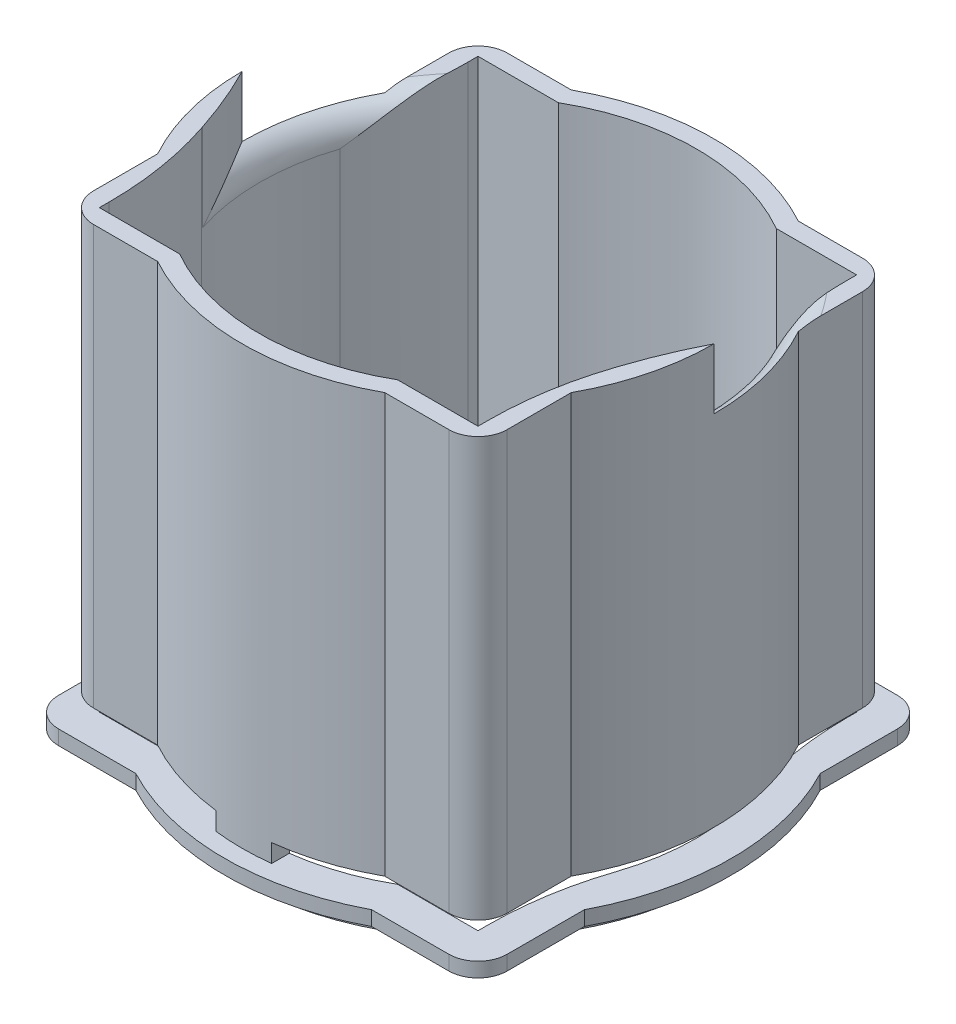
SolidWorks part; units mm, degrees
ref_plane "Front Plane" through (0, 0, 0) normal (0, 0, 1) x (1, 0, 0)
ref_plane "Top Plane" through (0, 0, 0) normal (0, 1, 0) x (1, 0, 0)
ref_plane "Right Plane" through (0, 0, 0) normal (1, 0, 0) x (0, 0, -1)
sketch "Sketch1" plane through (0, 0, 0) normal (0, 1, 0) x (1, 0, 0)
  line L0 (23.7595, 41.275) -> (41.275, 41.275)
  line L1 (-41.275, -41.275) -> (-23.7595, -41.275)
  line L2 (-41.275, -41.275) -> (-41.275, -23.7595)
  line L3 (-41.275, 41.275) -> (-23.7595, 41.275)
  line L4 (41.275, -41.275) -> (41.275, -23.7595)
  line L5 (-41.275, -41.275) -> (41.275, 41.275) construction
  line L6 (-41.275, 41.275) -> (41.275, -41.275) construction
  line L7 (41.275, 23.7595) -> (41.275, 41.275)
  line L8 (-41.275, 23.7595) -> (-41.275, 41.275)
  line L9 (23.7595, -41.275) -> (41.275, -41.275)
  line L10 (24.7569, 45.085) -> (45.085, 45.085)
  line L11 (45.085, 24.7569) -> (45.085, 45.085)
  line L12 (45.085, -45.085) -> (45.085, -24.7569)
  line L13 (24.7569, -45.085) -> (45.085, -45.085)
  line L14 (-45.085, -45.085) -> (-24.7569, -45.085)
  line L15 (-45.085, -45.085) -> (-45.085, -24.7569)
  line L16 (-45.085, 24.7569) -> (-45.085, 45.085)
  line L17 (-45.085, 45.085) -> (-24.7569, 45.085)
  arc A1 (-41.275, 23.7595) -> (-41.275, -23.7595) centre (0, 0) ccw
  arc A2 (23.7595, 41.275) -> (-23.7595, 41.275) centre (0, 0) ccw
  arc A3 (-23.7595, -41.275) -> (23.7595, -41.275) centre (0, 0) ccw
  arc A4 (41.275, -23.7595) -> (41.275, 23.7595) centre (0, 0) ccw
  arc A5 (45.085, -24.7569) -> (45.085, 24.7569) centre (0, 0) ccw
  arc A6 (-24.7569, -45.085) -> (24.7569, -45.085) centre (0, 0) ccw
  arc A7 (-45.085, 24.7569) -> (-45.085, -24.7569) centre (0, 0) ccw
  arc A8 (24.7569, 45.085) -> (-24.7569, 45.085) centre (0, 0) ccw
  point P0 (0, 0)
  dimension "D1" = 82.55
  dimension "D2" = 82.55
  dimension "D3" = 95.25
  dimension "D4" = 3.81
extrude "Boss-Extrude1" add sketch "Sketch1" along normal blind 101.6
sketch "Sketch6" plane through (0, 0, 0) normal (0, 0, 1) x (1, 0, 0)
  line L1 (-56.642, 10.287) -> (-6.096, 10.287)
  line L2 (-56.642, 10.287) -> (-56.642, 6.35)
  line L3 (-56.642, 6.35) -> (-6.096, 6.35)
  line L5 (-45.085, 0) -> (-24.7569, 0) construction
  line L8 (-6.096, 10.287) -> (-6.096, 6.35)
  line L9 (0, 0) -> (0, 21.9448) construction
  line L10 (6.096, 10.287) -> (6.096, 6.35)
  line L11 (56.642, 6.35) -> (6.096, 6.35)
  line L12 (56.642, 10.287) -> (6.096, 10.287)
  line L13 (56.642, 10.287) -> (56.642, 6.35)
  dimension "D3" = 3.937
  dimension "D1" = 6.096
  dimension "D4" = 6.35
extrude "Cut-Extrude4" cut sketch "Sketch6" against normal through all both and the other way through all
ref_plane "Plane1" through (0, 69.85, 0) normal (0, 1, 0) x (1, 0, 0)
sketch "Sketch12" plane through (0, 101.6, 0) normal (0, -1, 0) x (1, 0, 0)
  line L0 (25.7155, -48.895) -> (48.895, -48.895)
  line L1 (48.895, -48.895) -> (48.895, -25.7155)
  line L2 (48.895, 25.7155) -> (48.895, 48.895)
  line L3 (48.895, 48.895) -> (25.7155, 48.895)
  line L4 (-25.7155, 48.895) -> (-48.895, 48.895)
  line L5 (-48.895, 48.895) -> (-48.895, 25.7155)
  line L6 (-48.895, -25.7155) -> (-48.895, -48.895)
  line L7 (-48.895, -48.895) -> (-25.7155, -48.895)
  line L8 (24.7569, -45.085) -> (45.085, -45.085)
  line L9 (45.085, -45.085) -> (45.085, -24.7569)
  line L10 (45.085, 24.7569) -> (45.085, 45.085)
  line L11 (45.085, 45.085) -> (24.7569, 45.085)
  line L12 (-24.7569, 45.085) -> (-45.085, 45.085)
  line L13 (-45.085, 45.085) -> (-45.085, 24.7569)
  line L14 (-45.085, -24.7569) -> (-45.085, -45.085)
  line L15 (-45.085, -45.085) -> (-24.7569, -45.085)
  line L16 (24.7569, -45.085) -> (45.085, -45.085)
  line L17 (45.085, -45.085) -> (45.085, -24.7569)
  line L18 (45.085, 24.7569) -> (45.085, 45.085)
  line L19 (45.085, 45.085) -> (24.7569, 45.085)
  line L20 (-24.7569, 45.085) -> (-45.085, 45.085)
  line L21 (-45.085, 45.085) -> (-45.085, 24.7569)
  line L22 (-45.085, -24.7569) -> (-45.085, -45.085)
  line L23 (-45.085, -45.085) -> (-24.7569, -45.085)
  arc A0 (48.895, -25.7155) -> (48.895, 25.7155) centre (0, 0) ccw
  arc A3 (25.7155, 48.895) -> (-25.7155, 48.895) centre (0, 0) ccw
  arc A4 (-48.895, 25.7155) -> (-48.895, -25.7155) centre (0, 0) ccw
  arc A5 (-25.7155, -48.895) -> (25.7155, -48.895) centre (0, 0) ccw
  arc A7 (-24.7569, -45.085) -> (24.7569, -45.085) centre (0, 0) ccw
  arc A8 (45.085, -24.7569) -> (45.085, 24.7569) centre (0, 0) ccw
  arc A9 (24.7569, 45.085) -> (-24.7569, 45.085) centre (0, 0) ccw
  arc A10 (-45.085, 24.7569) -> (-45.085, -24.7569) centre (0, 0) ccw
  arc A11 (-24.7569, -45.085) -> (24.7569, -45.085) centre (0, 0) ccw
  arc A12 (45.085, -24.7569) -> (45.085, 24.7569) centre (0, 0) ccw
  arc A13 (24.7569, 45.085) -> (-24.7569, 45.085) centre (0, 0) ccw
  arc A14 (-45.085, 24.7569) -> (-45.085, -24.7569) centre (0, 0) ccw
  dimension "D1" = 0
  dimension "D2" = 3.81
extrude "Boss-Extrude9" add sketch "Sketch12" along normal blind 3.175 from surface starting at face at (-30.0451, 6.35, 0)
sketch "Sketch13" plane through (0, 0, 0) normal (0, 0, 1) x (1, 0, 0)
  line L0 (24.7569, 101.6) -> (-24.7569, 101.6) construction
  line L1 (-51.435, 101.6) -> (51.435, 101.6)
  line L2 (-51.435, 101.6) -> (-51.435, 88.9)
  line L3 (-51.435, 88.9) -> (51.435, 88.9)
  line L4 (51.435, 101.6) -> (51.435, 88.9)
  line L9 (-45.085, 101.6) -> (-51.435, 101.6) construction
  line L10 (51.435, 101.6) -> (45.085, 101.6) construction
  dimension "D1" = 12.7
extrude "Cut-Extrude6" cut sketch "Sketch13" against normal through all
fillet "Fillet1" radius 76.2 8 edges at (41.275, 55.9435, 23.7595) (-41.275, 55.9435, 23.7595) (-41.275, 3.175, -23.7595) (-41.275, 3.175, 23.7595) (41.275, 3.175, 23.7595) (41.275, 3.175, -23.7595) (-41.275, 49.5935, -23.7595) (41.275, 49.5935, -23.7595)
fillet "Fillet2" radius 101.6 2 edges at (-47.625, 95.25, 0) (47.625, 95.25, 0)
fillet "Fillet5" radius 6.35 2 edges at (-47.6248, 88.9, -0.1363) (47.6248, 88.9, -0.1363) tangent propagation no
fillet "Fillet6" radius 6.35 12 edges at (45.085, 1.5875, 45.085) (48.895, 4.7625, 48.895) (45.085, 1.5875, -45.085) (48.895, 4.7625, -48.895) (-45.085, 1.5875, -45.085) (-48.895, 4.7625, -48.895) (-45.085, 1.5875, 45.085) (-48.895, 4.7625, 48.895) (-45.085, 49.5935, -45.085) (45.085, 49.5935, -45.085) (45.085, 55.9435, 45.085) (-45.085, 55.9435, 45.085)
equation "\"tightTol\"= 0.005in"
equation "\"normTol\"= 0.01in"
equation "\"looseTol\"= 0.02in"
equation "\"D1@Sketch6\" = 0.250000in - \"normTol\""
equation "\"D3@Sketch6\"=1.5*\"looseTol\"+0.125000in"
